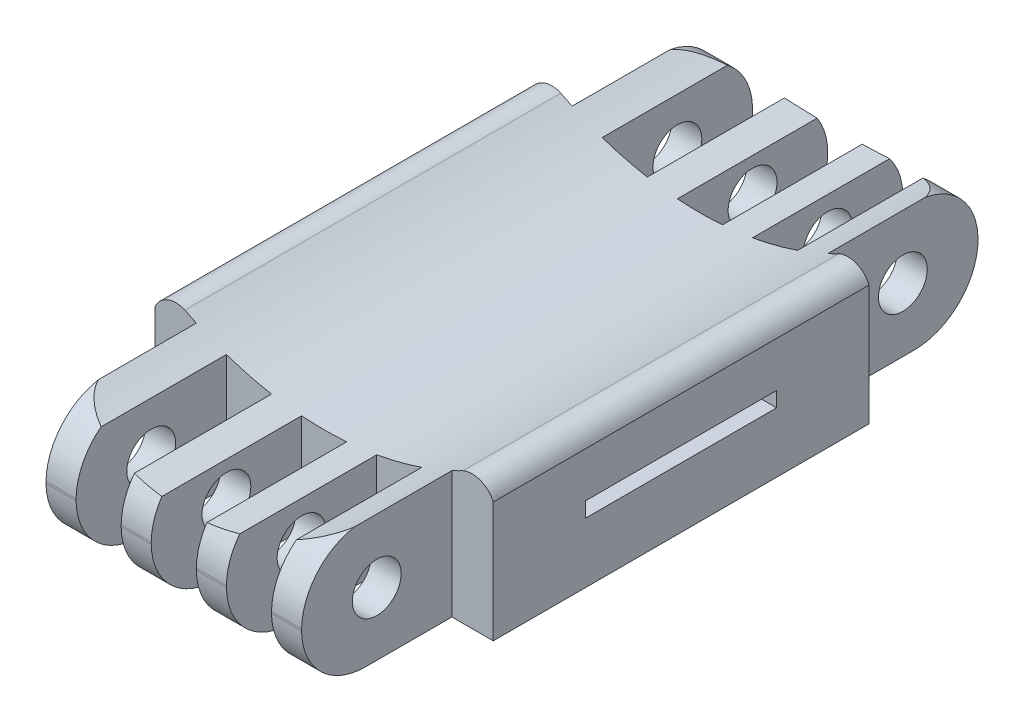
SolidWorks part; units mm, degrees
ref_plane "Front Plane" through (0, 0, 0) normal (0, 0, 1) x (1, 0, 0)
ref_plane "Top Plane" through (0, 0, 0) normal (0, 1, 0) x (1, 0, 0)
ref_plane "Right Plane" through (0, 0, 0) normal (1, 0, 0) x (0, 0, -1)
sketch "Sketch1" plane through (0, 0, 0) normal (0, 1, 0) x (1, 0, 0)
  line L31 (-17, 74) -> (-13, 74)
  line L32 (-7, 74) -> (-5, 74)
  line L33 (-12.5, 94) -> (-7.5, 94)
  line L35 (-7, 74) -> (-3, 74)
  line L37 (-2.5, 94) -> (2.5, 94)
  line L39 (3, 74) -> (7, 74)
  line L41 (7.5, 94) -> (12.5, 94)
  line L43 (13, 74) -> (17, 74)
  line L45 (17.5, 94) -> (22.5, 94)
  line L47 (-17.5, 94) -> (-22.5, 94)
  line L48 (-22.5, 94) -> (-22.5, 144)
  line L49 (-17.5, 144) -> (-22.5, 144)
  line L51 (-17, 164) -> (-13, 164)
  line L53 (-12.5, 144) -> (-7.5, 144)
  line L55 (-7, 164) -> (-3, 164)
  line L57 (-2.5, 144) -> (2.5, 144)
  line L59 (3, 164) -> (7, 164)
  line L61 (7.5, 144) -> (12.5, 144)
  line L63 (13, 164) -> (17, 164)
  line L65 (17.5, 144) -> (22.5, 144)
  line L66 (22.5, 144) -> (22.5, 94)
  line L89 (-15, 74) -> (-13, 74)
  line L92 (5, 74) -> (7, 74)
  line L94 (-15, 164) -> (-17, 164)
  line L95 (-17, 164) -> (-17, 144)
  line L96 (-17, 144) -> (-17.5, 144)
  line L97 (-15, 164) -> (-13, 164)
  line L98 (-13, 164) -> (-13, 144)
  line L99 (-13, 144) -> (-12.5, 144)
  line L100 (-5, 164) -> (-7, 164)
  line L101 (-7, 164) -> (-7, 144)
  line L102 (-7, 144) -> (-7.5, 144)
  line L103 (-5, 164) -> (-3, 164)
  line L104 (-3, 164) -> (-3, 144)
  line L105 (-3, 144) -> (-2.5, 144)
  line L106 (5, 164) -> (3, 164)
  line L107 (3, 164) -> (3, 144)
  line L108 (3, 144) -> (2.5, 144)
  line L109 (5, 164) -> (7, 164)
  line L110 (7, 164) -> (7, 144)
  line L111 (7, 144) -> (7.5, 144)
  line L112 (15, 164) -> (13, 164)
  line L113 (13, 164) -> (13, 144)
  line L114 (13, 144) -> (12.5, 144)
  line L115 (15, 164) -> (17, 164)
  line L116 (17, 164) -> (17, 144)
  line L117 (17, 144) -> (17.5, 144)
  line L118 (-17.5, 94) -> (-17, 94)
  line L119 (-17, 94) -> (-17, 74)
  line L120 (-17, 74) -> (-13, 74)
  line L121 (-13, 74) -> (-13, 94)
  line L122 (-13, 94) -> (-12.5, 94)
  line L123 (-7.5, 94) -> (-7, 94)
  line L124 (-7, 94) -> (-7, 74)
  line L125 (-7, 74) -> (-3, 74)
  line L126 (-3, 74) -> (-3, 94)
  line L127 (-3, 94) -> (-2.5, 94)
  line L128 (2.5, 94) -> (3, 94)
  line L129 (3, 94) -> (3, 74)
  line L130 (3, 74) -> (7, 74)
  line L131 (7, 74) -> (7, 94)
  line L132 (7, 94) -> (7.5, 94)
  line L133 (12.5, 94) -> (13, 94)
  line L134 (13, 94) -> (13, 74)
  line L135 (17, 74) -> (17, 94)
  line L136 (17, 94) -> (17.5, 94)
extrude "Boss-Extrude1" add sketch "Sketch1" along normal blind 20 contours L135 L136 L45 L66 L65 L117 L116 L63 L113 L114 L61 L111 L110 L59 L107 L108 L57 L105 L104 L55 L101 L102 L53 L99 L98 L51 L95 L96 L49 L48 L47 L118 L119 L31 L121 L122 L33 L123 L124 L32 L35 L126 L127 L37 L128 L129 region at (0, 0, -119)
sketch "Sketch2" plane through (0, 0, 50) normal (0, 0, 1) x (1, 0, 0)
  line L0 (-22.5, 20) -> (22.5, 20)
  line L1 (-22.5, 20) -> (-22.5, 16)
  line L2 (-22.5, 20) -> (-22.5, 0) construction
  line L4 (22.5, 20) -> (22.5, 0) construction
  line L5 (22.5, 16) -> (22.5, 20)
  arc A0 (-18.5, 17.6071) -> (18.5, 17.6071) centre (0, 53.0719) ccw
  arc A1 (-22.5, 16) -> (-18.5, 17.6071) centre (-19.6964, 14.8036) cw
  arc A2 (18.5, 17.6071) -> (22.5, 16) centre (19.6964, 14.8036) cw
sketch "Sketch7" plane through (22.5, 0, 0) normal (1, 0, 0) x (0, 0, -1)
  line L0 (82.4991, 17) -> (93.9991, 17)
  line L1 (73.9991, 20) -> (73.9991, 0)
  line L2 (155.4991, 0) -> (163.9991, 0)
  line L3 (82.4991, 20) -> (73.9991, 20)
  line L4 (155.4991, 17) -> (143.9991, 17)
  line L5 (73.9991, 0) -> (73.9991, 17)
  line L6 (82.4991, 0) -> (73.9991, 0)
  line L8 (155.4991, 20) -> (163.9991, 20)
  line L14 (93.9991, 17) -> (93.9991, 20)
  line L15 (93.9991, 20) -> (82.4991, 20)
  line L16 (143.9991, 17) -> (143.9991, 20)
  line L17 (143.9991, 20) -> (155.4991, 20)
  line L22 (163.9991, 20) -> (164.814, 20)
  line L23 (164.814, 20) -> (164.814, 0)
  line L24 (164.814, 0) -> (163.9991, 0)
  arc A0 (82.4991, 0) -> (82.4991, 17) centre (82.4991, 8.5) cw
  arc A1 (155.4991, 0) -> (155.4991, 17) centre (155.4991, 8.5) ccw
extrude "Cut-Extrude21" cut sketch "Sketch7" against normal blind 45 contours L1 A0 L0 L14 L15 L3 | L6 A0 L5 | A1 L8 L17 L16 L4 | A1 L2 region at (22.5, 17.8021, -82.3355) region at (22.5, 1.8986, -75.8978) region at (22.5, 8.5, -164.2878)
extrude "Cut-Extrude23" cut sketch "Sketch2" against normal blind 444
sketch "Sketch9" plane through (22.5, 0, 0) normal (1, 0, 0) x (0, 0, -1)
  circle A4 centre (153.9996, 8.466) radius 3.25
  circle A5 centre (84, 8.4051) radius 3.25
  circle A6 centre (178, 8.5) radius 3.15
  circle A7 centre (60, 8.5) radius 3.15
extrude "Cut-Extrude24" cut sketch "Sketch9" against normal blind 45
sketch "Sketch12" plane through (0, 0, 50) normal (0, 0, 1) x (1, 0, 0)
  line L0 (-1, 3.35) -> (-1, 6.55)
  line L3 (1, 3.35) -> (-1, 3.35)
  line L4 (1, 6.55) -> (1, 3.35)
  line L5 (0, 6.55) -> (1, 6.55)
  line L6 (0, 6.55) -> (-1, 6.55)
extrude "Cut-Extrude26" cut sketch "Sketch12" against normal blind 444
sketch "Sketch13" plane through (22.5, 0, 0) normal (1, 0, 0) x (0, 0, -1)
  line L2 (119, 8) -> (131.7, 8)
  line L3 (131.7, 8) -> (131.7, 10)
  line L4 (119, 8) -> (106.3, 8)
  line L5 (106.3, 8) -> (106.3, 10)
  line L6 (106.3, 10) -> (131.7, 10)
extrude "Cut-Extrude27" cut sketch "Sketch13" against normal blind 45
